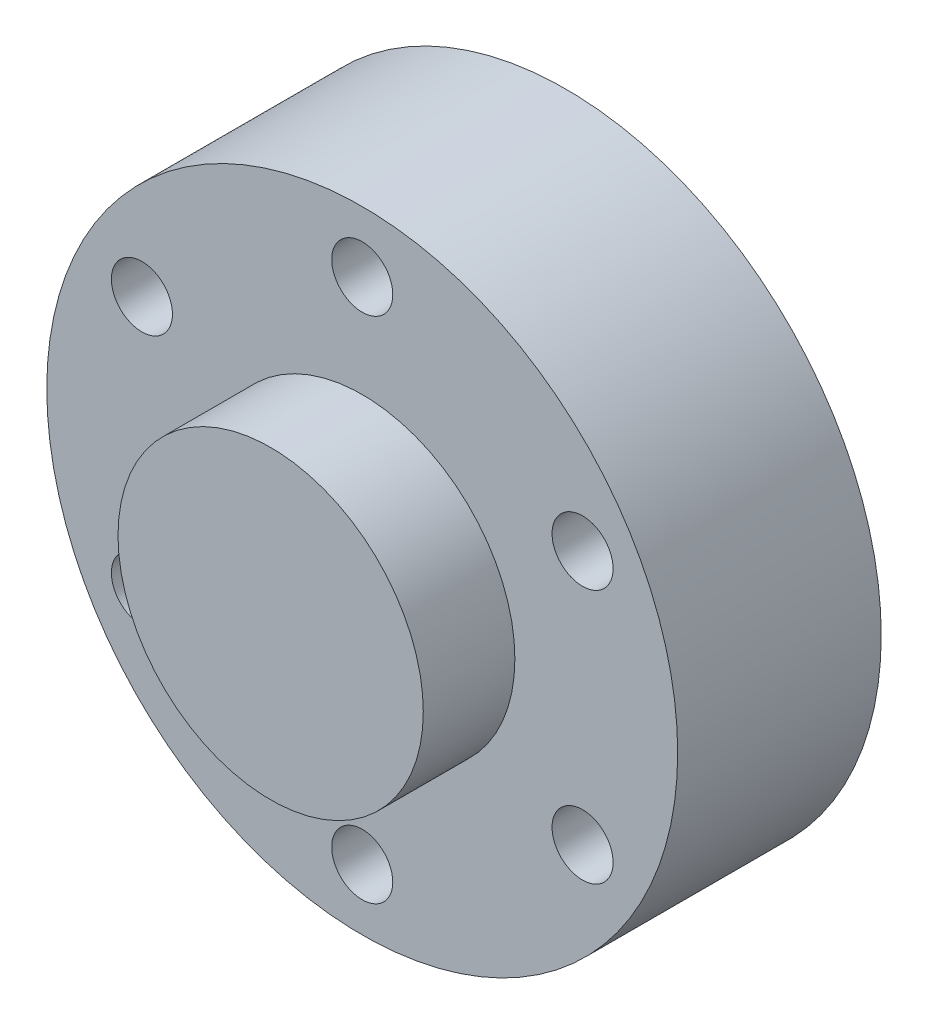
SolidWorks part; units mm, degrees
ref_plane "Front Plane" through (0, 0, 0) normal (0, 0, 1) x (1, 0, 0)
ref_plane "Top Plane" through (0, 0, 0) normal (0, 1, 0) x (1, 0, 0)
ref_plane "Right Plane" through (0, 0, 0) normal (1, 0, 0) x (0, 0, -1)
sketch "Sketch2" plane through (0, 0, 0) normal (0, 0, 1) x (1, 0, 0)
  line L0 (0, 20.3178) -> (0, -21.083) construction
  circle A0 centre (0, 0) radius 9.5
  circle A1 centre (0, 0) radius 12.5 construction
  circle A3 centre (0, 0) radius 15.5
  circle A4 centre (0, 12.5) radius 1.5
  circle A5 centre (10.8253, 6.25) radius 1.5
  circle A6 centre (10.8253, -6.25) radius 1.5
  circle A7 centre (0, -12.5) radius 1.5
  circle A8 centre (-10.8253, -6.25) radius 1.5
  circle A9 centre (-10.8253, 6.25) radius 1.5
  point P21 (1.7321, -1)
  point P22 (0, 0)
  dimension "D1" = 19
  dimension "D2" = 6
  dimension "D3" = 25
  dimension "D4" = 31
  dimension "D5" = 3
extrude "Boss-Extrude1" add sketch "Sketch2" along normal blind 10 contours A3 A9 A8 A7 A6 A5 A4 A0 | A0 region at (0, 0, 0) region at (-15.0616, 0, 0)
sketch "Sketch3" plane through (0, 0, 10) normal (0, 0, 1) x (1, 0, 0)
  circle A0 centre (0, 0) radius 7.5
  dimension "D1" = 15
extrude "Boss-Extrude2" add sketch "Sketch3" along normal blind 4.5
sketch "Sketch6" plane through (0, 0, 0) normal (0, 0, -1) x (-1, 0, 0)
  circle A0 centre (0, 0) radius 7.5
  dimension "D1" = 15
extrude "Boss-Extrude4" add sketch "Sketch6" along normal blind 4.5 contours A0
sketch "Sketch7" plane through (0, 0, -4.5) normal (0, 0, -1) x (-1, 0, 0)
  circle A0 centre (0, 0) radius 2
  dimension "D1" = 4
extrude "Boss-Extrude5" add sketch "Sketch7" along normal blind 1
fillet "Fillet2" radius 0.05 1 edges at (-2, 0, -5.5)
sketch "Sketch9" plane through (0, 0, -5.5) normal (0, 0, -1) x (-1, 0, 0)
  line L1 (-1.2247, 1.25) -> (1.2247, 1.25)
  arc A0 (-1.2247, 1.25) -> (1.2247, 1.25) centre (0, 0) ccw
  circle A1 centre (0, -0.25) radius 1.5 construction
  dimension "D1" = 3.5
  dimension "D2" = 3
extrude "Cut-Extrude1" cut sketch "Sketch9" against normal blind 11
